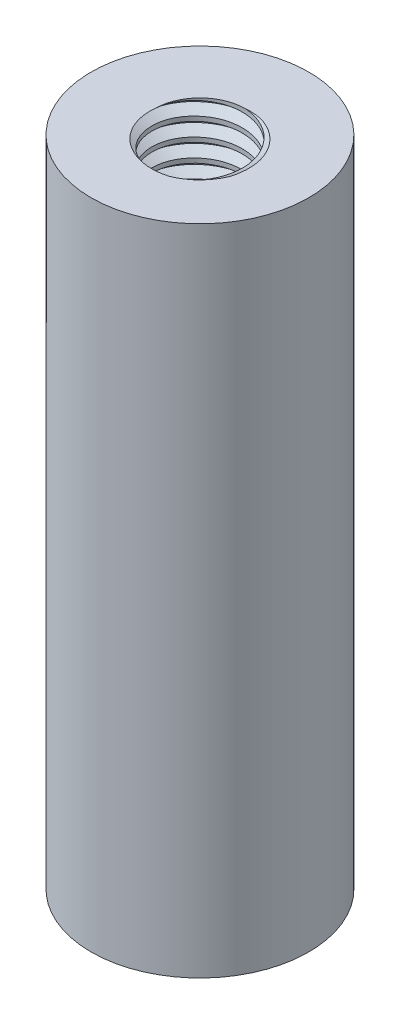
SolidWorks part; units mm, degrees
ref_plane "Front Plane" through (0, 0, 0) normal (0, 0, 1) x (1, 0, 0)
ref_plane "Top Plane" through (0, 0, 0) normal (0, 1, 0) x (1, 0, 0)
ref_plane "Right Plane" through (0, 0, 0) normal (1, 0, 0) x (0, 0, -1)
sketch "Sketch1" plane through (0, 0, 0) normal (0, 1, 0) x (1, 0, 0)
  circle A0 centre (0, 0) radius 3
  dimension "D1" = 6
extrude "Boss-Extrude1" add sketch "Sketch1" along normal blind 9
sketch "Sketch2" plane through (0, 9, 0) normal (0, 1, 0) x (1, 0, 0)
  circle A0 centre (0, 0) radius 1.25
  dimension "D1" = 2.5
extrude "Cut-Extrude1" cut sketch "Sketch2" against normal blind 8.5
thread "Thread1" pitch 0.5 method cut profile "Thread Profile1" start angle 0, offset 2, length 10, pitch 0.5, diameter 2.5
ref_plane "Plane1" through (-1.25, 11, 0) normal (0, 0, 1) x (-1, 0, 0)
sketch "Thread Profile1" plane through (-1.25, 11, 0) normal (0, 0, 1) x (-1, 0, 0)
  line L0 (0, 0) -> (0, 0.5) construction
  line L1 (0, 0) -> (0.2706, 0.1562)
  line L2 (0.2706, 0.1562) -> (0.2706, 0.2187)
  line L3 (0.2706, 0.2187) -> (0, 0.375)
  line L4 (0.2706, 0.1875) -> (0, 0.1875) construction
  line L11 (0, 0) -> (0, 0.375)
  point P2 (0, 0)
  dimension "Pitch" = 0.5
  dimension "Profile_Angle" = 60
  dimension "Profile_Land" = 0.0625
  dimension "Profile_Height" = 0.2706
mirror "Mirror1" about plane through (0, 0, 0) normal (0, 1, 0) of bodies 103
